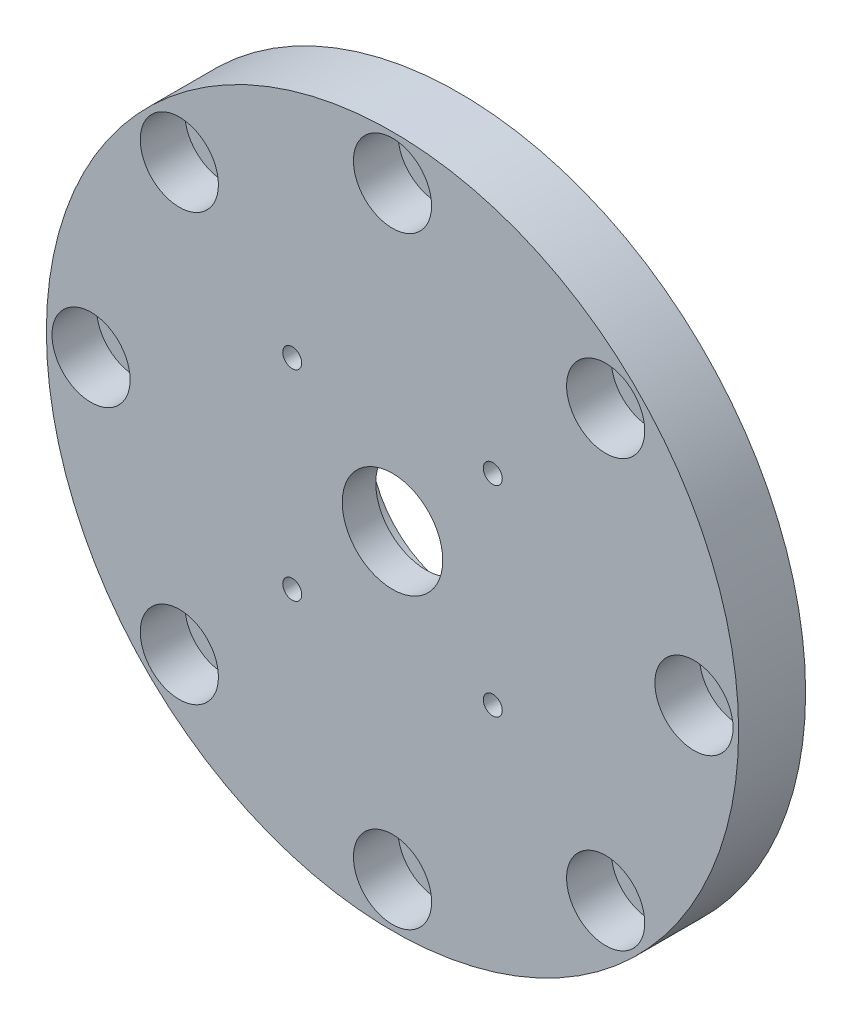
SolidWorks part; units mm, degrees
ref_plane "Front Plane" through (0, 0, 0) normal (0, 0, 1) x (1, 0, 0)
ref_plane "Top Plane" through (0, 0, 0) normal (0, 1, 0) x (1, 0, 0)
ref_plane "Right Plane" through (0, 0, 0) normal (1, 0, 0) x (0, 0, -1)
sketch "Sketch1" plane through (0, 0, 0) normal (0, 0, 1) x (1, 0, 0)
  line L11 (0, 0) -> (8.9803, 8.9803) construction
  line L17 (0, 0) -> (-27, 0) construction
  circle A2 centre (0, 0) radius 4.5
  circle A3 centre (0, 0) radius 12.7 construction
  circle A11 centre (8.9803, 8.9803) radius 0.85
  circle A12 centre (8.9803, -8.9803) radius 0.85
  circle A13 centre (-8.9803, -8.9803) radius 0.85
  circle A14 centre (-8.9803, 8.9803) radius 0.85
  circle A33 centre (0, 0) radius 24 construction
  circle A34 centre (0, 0) radius 31
  circle A35 centre (-27, 0) radius 1.55
  circle A36 centre (-19.0919, 19.0919) radius 1.55
  circle A37 centre (0, 27) radius 1.55
  circle A38 centre (19.0919, 19.0919) radius 1.55
  circle A39 centre (27, 0) radius 1.55
  circle A40 centre (19.0919, -19.0919) radius 1.55
  circle A41 centre (0, -27) radius 1.55
  circle A42 centre (-19.0919, -19.0919) radius 1.55
  point P7 (0, 0)
  point P10 (0, 0)
  point P12 (0, 0)
  point P16 (0, 0)
  point P17 (0, 0)
  point P20 (0, 0)
  point P30 (0, 0)
  point P39 (0, 0)
  point P47 (0, 0)
  point P64 (0, 0)
  dimension "D1" = 4
extrude "Boss-Extrude2" add sketch "Sketch1" along normal blind 6
sketch "Sketch5" plane through (0, 0, 0) normal (0, 0, -1) x (-1, 0, 0)
  circle A0 centre (0, 0) radius 8
extrude "Cut-Extrude3" cut sketch "Sketch5" against normal blind 3
sketch "Sketch6" plane through (0, 0, 6) normal (0, 0, 1) x (1, 0, 0)
  circle A7 centre (0, 27) radius 3.5
  circle A8 centre (19.0919, 19.0919) radius 3.5
  circle A9 centre (27, 0) radius 3.5
  circle A10 centre (19.0919, -19.0919) radius 3.5
  circle A11 centre (0, -27) radius 3.5
  circle A12 centre (-19.0919, -19.0919) radius 3.5
  circle A13 centre (-27, 0) radius 3.5
  circle A14 centre (-19.0919, 19.0919) radius 3.5
  point P11 (-3.75, 3.75)
  point P29 (0, 0)
  point P31 (0, 0)
  dimension "D2" = 8
extrude "Cut-Extrude4" cut sketch "Sketch6" against normal blind 4
sketch "Sketch7" plane through (0, 0, 0) normal (0, 0, -1) x (-1, 0, 0)
  line L0 (-8.9803, 11.3403) -> (-8.9803, 6.6203) construction
  line L1 (-11.0241, 7.8003) -> (-6.9364, 10.1603) construction
  line L2 (-6.9364, 7.8003) -> (-11.0241, 10.1603) construction
  line L3 (-6.9364, 10.1603) -> (-8.9803, 11.3403)
  line L4 (-8.9803, 11.3403) -> (-11.0241, 10.1603)
  line L5 (-11.0241, 10.1603) -> (-11.0241, 7.8003)
  line L6 (-11.0241, 7.8003) -> (-8.9803, 6.6203)
  line L7 (-8.9803, 6.6203) -> (-6.9364, 7.8003)
  line L8 (-6.9364, 7.8003) -> (-6.9364, 10.1603)
  line L9 (10.1603, 6.9364) -> (11.3403, 8.9803)
  line L10 (11.3403, 8.9803) -> (10.1603, 11.0241)
  line L11 (10.1603, 11.0241) -> (7.8003, 11.0241)
  line L12 (7.8003, 11.0241) -> (6.6203, 8.9803)
  line L13 (6.6203, 8.9803) -> (7.8003, 6.9364)
  line L14 (7.8003, 6.9364) -> (10.1603, 6.9364)
  line L15 (11.3403, 8.9803) -> (6.6203, 8.9803) construction
  line L16 (7.8003, 11.0241) -> (10.1603, 6.9364) construction
  line L17 (7.8003, 6.9364) -> (10.1603, 11.0241) construction
  line L18 (6.9364, -10.1603) -> (8.9803, -11.3403)
  line L19 (8.9803, -11.3403) -> (11.0241, -10.1603)
  line L20 (11.0241, -10.1603) -> (11.0241, -7.8003)
  line L21 (11.0241, -7.8003) -> (8.9803, -6.6203)
  line L22 (8.9803, -6.6203) -> (6.9364, -7.8003)
  line L23 (6.9364, -7.8003) -> (6.9364, -10.1603)
  line L24 (8.9803, -11.3403) -> (8.9803, -6.6203) construction
  line L25 (11.0241, -7.8003) -> (6.9364, -10.1603) construction
  line L26 (6.9364, -7.8003) -> (11.0241, -10.1603) construction
  line L27 (-10.1603, -6.9364) -> (-11.3403, -8.9803)
  line L28 (-11.3403, -8.9803) -> (-10.1603, -11.0241)
  line L29 (-10.1603, -11.0241) -> (-7.8003, -11.0241)
  line L30 (-7.8003, -11.0241) -> (-6.6203, -8.9803)
  line L31 (-6.6203, -8.9803) -> (-7.8003, -6.9364)
  line L32 (-7.8003, -6.9364) -> (-10.1603, -6.9364)
  line L33 (-11.3403, -8.9803) -> (-6.6203, -8.9803) construction
  line L34 (-7.8003, -11.0241) -> (-10.1603, -6.9364) construction
  line L35 (-7.8003, -6.9364) -> (-10.1603, -11.0241) construction
  circle A0 centre (-8.9803, 8.9803) radius 2.36 construction
  circle A1 centre (8.9803, 8.9803) radius 2.36 construction
  circle A2 centre (8.9803, -8.9803) radius 2.36 construction
  circle A3 centre (-8.9803, -8.9803) radius 2.36 construction
  point P8 (-8.9803, 8.9803)
  point P11 (-8.9803, 8.9803)
  point P20 (8.9803, 8.9803)
  point P23 (8.9803, 8.9803)
  point P30 (8.9803, -8.9803)
  point P33 (8.9803, -8.9803)
  point P40 (-8.9803, -8.9803)
  point P43 (-8.9803, -8.9803)
  point P44 (0, 0)
  dimension "D1" = 4
extrude "Cut-Extrude5" cut sketch "Sketch7" against normal blind 2
